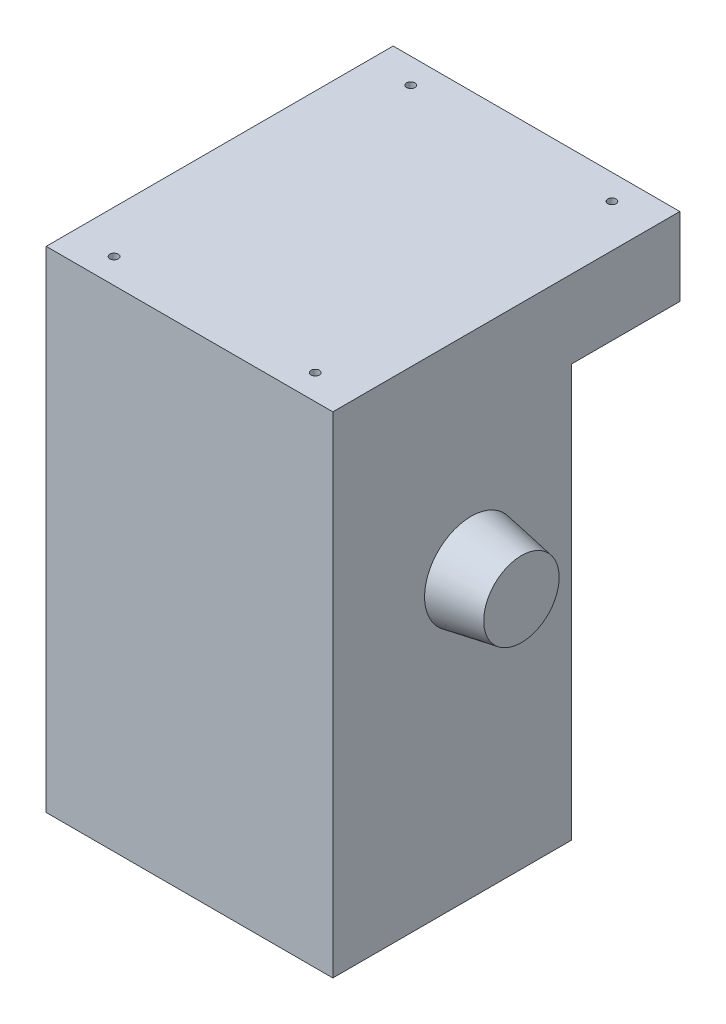
SolidWorks part; units mm, degrees
ref_plane "前视基准面" through (0, 0, 0) normal (0, 0, 1) x (1, 0, 0)
ref_plane "上视基准面" through (0, 0, 0) normal (0, 1, 0) x (1, 0, 0)
ref_plane "右视基准面" through (0, 0, 0) normal (1, 0, 0) x (0, 0, -1)
sketch "草图1" plane through (0, 0, 0) normal (0, 1, 0) x (1, 0, 0)
  line L1 (-57, 47.5) -> (57, 47.5)
  line L2 (-57, 47.5) -> (-57, -47.5)
  line L3 (-57, -47.5) -> (57, -47.5)
  line L4 (57, 47.5) -> (57, -47.5)
  line L5 (-57, 47.5) -> (57, -47.5) construction
  line L6 (-57, -47.5) -> (57, 47.5) construction
  point P0 (0, 0)
  dimension "D1" = 114
  dimension "D2" = 95
extrude "凸台-拉伸1" add sketch "草图1" along normal blind 164
sketch "草图2" plane through (0, 164, 0) normal (0, 1, 0) x (1, 0, 0)
  line L1 (-57, -47.5) -> (57, -47.5)
  line L2 (-57, -47.5) -> (-57, 90.5)
  line L3 (-57, 90.5) -> (57, 90.5)
  line L4 (57, -47.5) -> (57, 90.5)
  dimension "D1" = 114
  dimension "D2" = 138
extrude "凸台-拉伸2" add sketch "草图2" along normal blind 31
hole_wizard "M4 螺纹孔1" positions "草图3" profile "草图5" tap size "M4" standard "ISO"
sketch "草图3" plane through (0, 195, 0) normal (0, 1, 0) x (1, 0, 0)
  line L0 (-57, -47.5) -> (57, -47.5) construction
  line L1 (-57, 90.5) -> (-57, -47.5) construction
  point P0 (-40, -37.5)
  dimension "D1" = 10
  dimension "D2" = 17
sketch "草图5" plane through (-40, 195, 37.5) normal (1, 0, 0) x (0, 0, 1)
  line L0 (0, 0) -> (0, 8.9914)
  line L1 (0, 8.9914) -> (1.65, 8)
  line L2 (1.65, 8) -> (1.65, 0)
  line L5 (1.65, 0) -> (0, 0)
  line L10 (0, 8.9914) -> (-1.65, 8) construction
  line L11 (0, -6.35) -> (0, 107.95) construction
  dimension "螺纹孔钻头直径" = 3.3
  dimension "螺纹孔钻头深度" = 8
  dimension "导头角度" = 118
cosmetic thread "孔螺蚊线1" parameters "D1"=2.5, "D2"=4
pattern_linear "阵列(线性)1" count 2 spacing 118 along (0, 0, -1) count 2 spacing 80 along (1, 0, 0) of "M4 螺纹孔1"
sketch "草图6" plane through (57, 0, 0) normal (1, 0, 0) x (0, 0, -1)
  line L0 (-47.5, 0) -> (47.5, 0) construction
  line L1 (-47.5, 195) -> (-47.5, 0) construction
  circle A0 centre (7.5, 113) radius 15
  dimension "D3" = 30
  dimension "D1" = 113
  dimension "D2" = 55
extrude "凸台-拉伸3" add sketch "草图6" along normal blind 20
ref_axis "基准轴1" through (77, 113, -7.5) along (-1, 0, 0)
draft "拔模1" type of draft neutral plane draft angle 10 faces to draft 1 face at (77, 113, -22.5) neutral plane through (77, 113, -7.5) neutral plane normal (1, 0, 0) parameters "D1"=10
mirror "镜向1" about plane through (0, 0, 0) normal (1, 0, 0) of bodies 110
